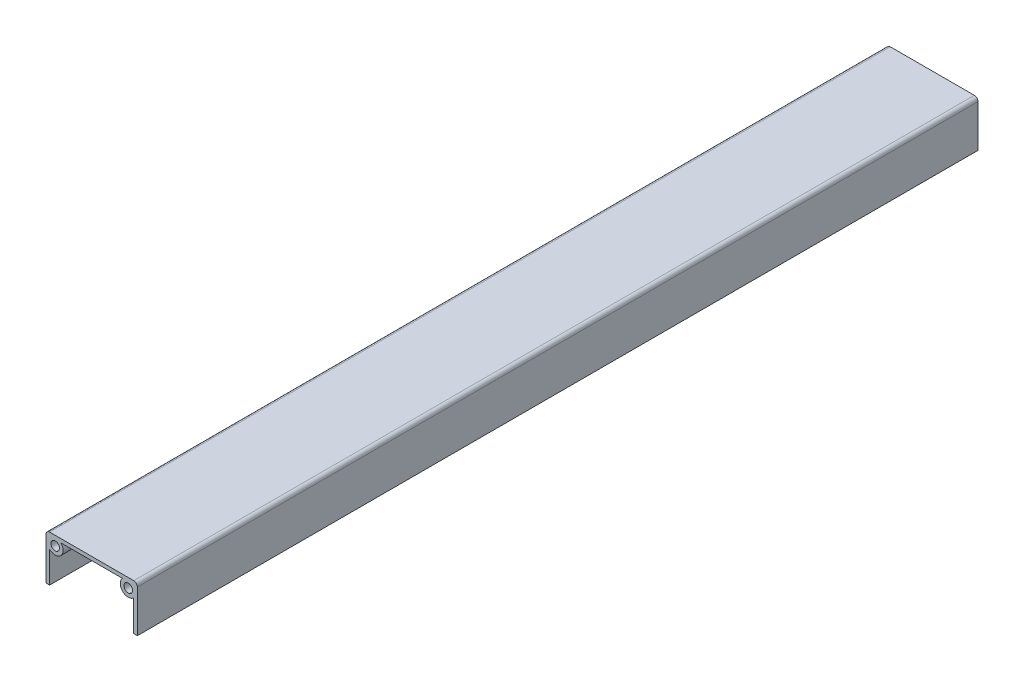
SolidWorks part; units mm, degrees
ref_plane "Front Plane" through (0, 0, 0) normal (0, 0, 1) x (1, 0, 0)
ref_plane "Top Plane" through (0, 0, 0) normal (0, 1, 0) x (1, 0, 0)
ref_plane "Right Plane" through (0, 0, 0) normal (1, 0, 0) x (0, 0, -1)
sketch "Sketch1" plane through (0, 0, 0) normal (0, 0, 1) x (1, 0, 0)
  line L0 (0, 31.75) -> (0, -31.75) construction
  line L1 (-31.75, -31.75) -> (31.75, -31.75)
  line L2 (-31.75, -31.75) -> (-31.75, 31.75)
  line L3 (-31.75, 31.75) -> (31.75, 31.75)
  line L4 (31.75, -31.75) -> (31.75, 31.75)
  line L5 (-31.75, -31.75) -> (31.75, 31.75) construction
  line L6 (-31.75, 31.75) -> (31.75, -31.75) construction
  line L7 (-31.75, 0) -> (31.75, 0) construction
  circle A0 centre (-25.4, 25.4) radius 3
  circle A1 centre (25.4, -25.4) radius 3
  circle A2 centre (-25.4, -25.4) radius 3
  circle A3 centre (25.4, 25.4) radius 3
  point P0 (0, 0)
  dimension "D3" = 6
  dimension "D9" = 50.8
  dimension "D4" = 50.8
  dimension "D1" = 63.5
  dimension "D2" = 63.5
  dimension "D5" = 6.35
extrude "Boss-Extrude1" add sketch "Sketch1" along normal mid plane 584.2
fillet "Fillet1" radius 2.54 4 edges at (-31.75, -31.75, 0) (31.75, -31.75, 0) (-31.75, 31.75, 0) (31.75, 31.75, 0)
shell "Shell1" thickness 2.54 removed face at (-28.4, -25.4, -292.1) removed face at (0, 0, 292.1)
sketch "Sketch3" plane through (0, 0, 292.1) normal (0, 0, 1) x (1, 0, 0)
  line L1 (-31.75, 29.21) -> (-31.75, -29.21) construction
  line L2 (-31.75, -0.1289) -> (31.9153, -0.1289)
  line L3 (-31.75, -0.1289) -> (-31.75, -31.8789)
  line L4 (-31.75, -31.8789) -> (31.9153, -31.8789)
  line L5 (31.9153, -0.1289) -> (31.9153, -31.8789)
  dimension "D1" = 31.75
extrude "Cut-Extrude2" cut sketch "Sketch3" against normal through all
equation "\"D1@Boss-Extrude1\"=\"robot_width@2016 Chassis 3.0.Assembly\"-6in"
